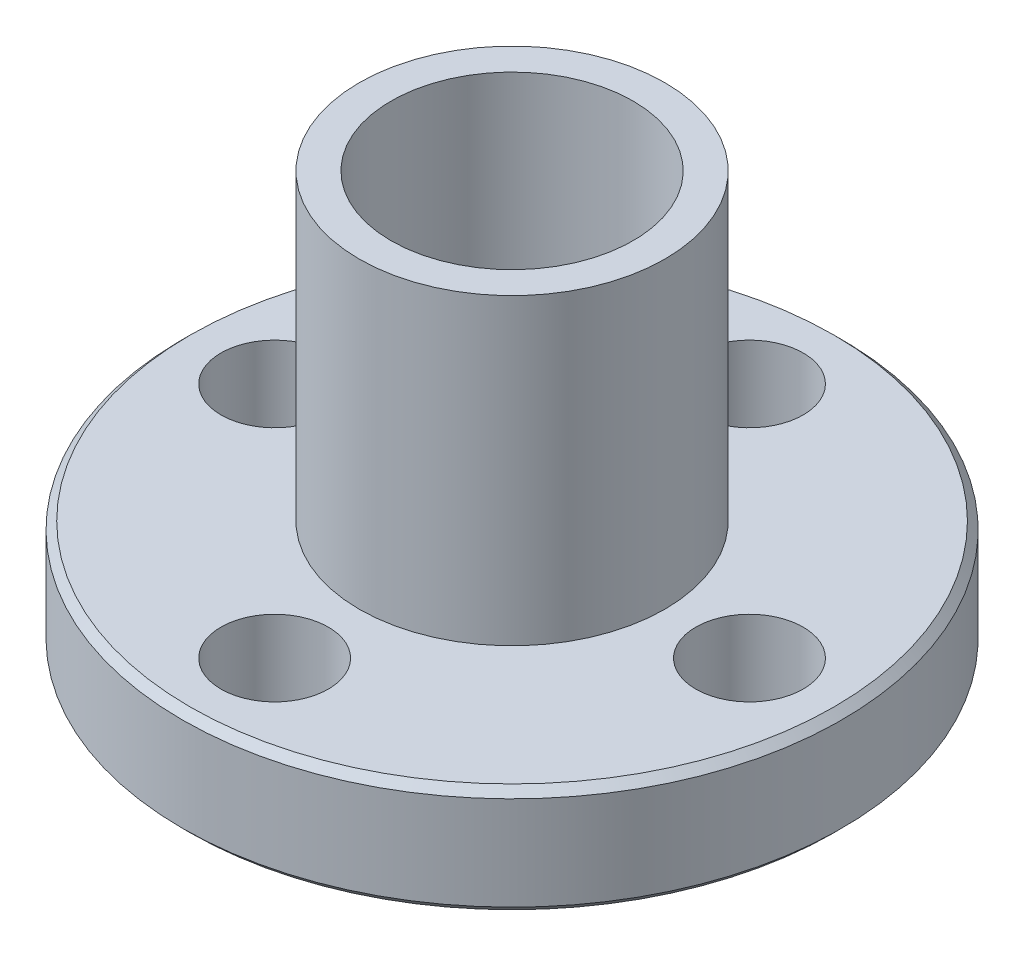
SolidWorks part; units mm, degrees
note: The reader was unsure of these and kept them because the rebuilt part matched: shared geometry of "Sketch1<3>".
material "Brass"
ref_plane "Front Plane" through (0, 0, 0) normal (0, 0, 1) x (1, 0, 0)
ref_plane "Top Plane" through (0, 0, 0) normal (0, 1, 0) x (1, 0, 0)
ref_plane "Right Plane" through (0, 0, 0) normal (1, 0, 0) x (0, 0, -1)
sketch "Sketch1" plane through (0, 0, 0) normal (0, 1, 0) x (1, 0, 0)
  circle A0 centre (0, 0) radius 10.8902
  circle A1 centre (0, 0) radius 5.05
  circle A2 centre (0, 0) radius 7.8453 construction
  circle A4 centre (0, 7.8453) radius 1.775
  circle A5 centre (7.8453, 0) radius 1.775
  circle A6 centre (0, 0) radius 7.8453 construction
  circle A7 centre (0, -7.8453) radius 1.775
  circle A8 centre (0, 0) radius 7.8453 construction
  circle A9 centre (-7.8453, 0) radius 1.775
  circle A10 centre (0, 0) radius 7.8453 construction
  circle A11 centre (0, 0) radius 4
  point P19 (0, 0)
  dimension "D1" = 21.7805
  dimension "D2" = 10.1
  dimension "D3" = 4
  dimension "D4" = 1.27
  dimension "D5" = 3.55
  dimension "D6" = 8
extrude "Boss-Extrude1" add sketch "Sketch1" against normal blind 3.6 contours A0 A9 A7 A5 A4 A1
extrude "Boss-Extrude2" add sketch "Sketch1<3>" along normal blind 10.02 and the other way offset from surface (5.7927 mm away) 2.1927 separate body contours A1 A11 other way up to face at (-7.8453, -3.6, 1.775)
sketch "Sketch1<3>" plane through (0, 0, 0) normal (0, 1, 0) x (1, 0, 0) same geometry as "Sketch1"
chamfer "Chamfer2" distance 0.25 angle 45 2 edges at (0, -3.6, 10.8902) (0, 0, 10.8902)
